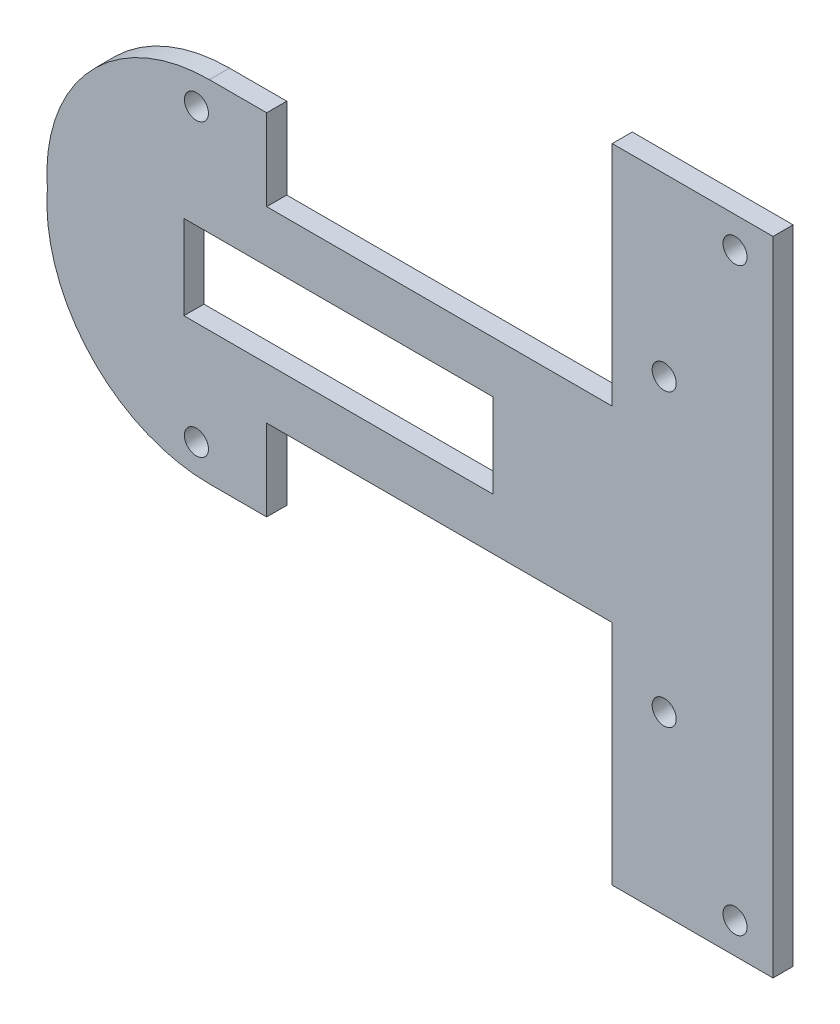
SolidWorks part; units mm, degrees
ref_plane "Plan de face" through (0, 0, 0) normal (0, 0, 1) x (1, 0, 0)
ref_plane "Plan de dessus" through (0, 0, 0) normal (0, 1, 0) x (1, 0, 0)
ref_plane "Plan de droite" through (0, 0, 0) normal (1, 0, 0) x (0, 0, -1)
sketch "Esquisse1" plane through (0, 0, 0) normal (0, 0, 1) x (1, 0, 0)
  line L45 (0, 80) -> (-40.0634, 80)
  line L46 (-40.0634, 80) -> (-40.0634, 43.608)
  line L51 (-140.4048, 43.608) -> (-126.1447, 43.608)
  line L52 (-126.1447, 43.608) -> (-126.1447, 23.3472)
  line L53 (-126.1447, 23.3472) -> (-40.0634, 23.3472)
  line L54 (-40.0634, 23.3472) -> (-40.0634, 43.608)
  line L56 (0, -80) -> (0, 80)
  line L57 (-40.0634, -80) -> (-40.0634, -43.608)
  line L58 (0, -80) -> (-40.0634, -80)
  line L59 (-40.0634, -23.3472) -> (-40.0634, -43.608)
  line L60 (-126.1447, -23.3472) -> (-40.0634, -23.3472)
  line L61 (-126.1447, -43.608) -> (-126.1447, -23.3472)
  line L62 (-140.4048, -43.608) -> (-126.1447, -43.608)
  arc A0 (-140.4048, 43.608) -> (-180.7891, 0) centre (-140.4048, 3.1046) ccw
  circle A3 centre (-143.653, 36.2066) radius 3
  circle A4 centre (-27.1131, 36.2066) radius 3
  circle A7 centre (-9.4671, 72.2918) radius 3
  circle A8 centre (-9.4671, -72.2918) radius 3
  circle A9 centre (-27.1131, -36.2066) radius 3
  circle A10 centre (-143.653, -36.2066) radius 3
  arc A11 (-140.4048, -43.608) -> (-180.7891, 0) centre (-140.4048, -3.1046) cw
extrude "Boss.-Extru.2" add sketch "Esquisse1" along normal blind 5
sketch "Esquisse2" plane through (0, 0, 5) normal (0, 0, 1) x (1, 0, 0)
  line L0 (-146.7768, -10.5) -> (-146.7768, 10.5)
  line L1 (-180.7891, 0) -> (0, 0) construction
  line L2 (-146.7768, 10.5) -> (-69.7768, 10.5)
  line L3 (-69.7768, 10.5) -> (-69.7768, -10.5)
  line L4 (-146.7768, -10.5) -> (-69.7768, -10.5)
  point P7 (-69.7768, 0)
  point P8 (-146.7768, 0)
extrude "Enlèv. mat.-Extru.2" cut sketch "Esquisse2" against normal blind 5
